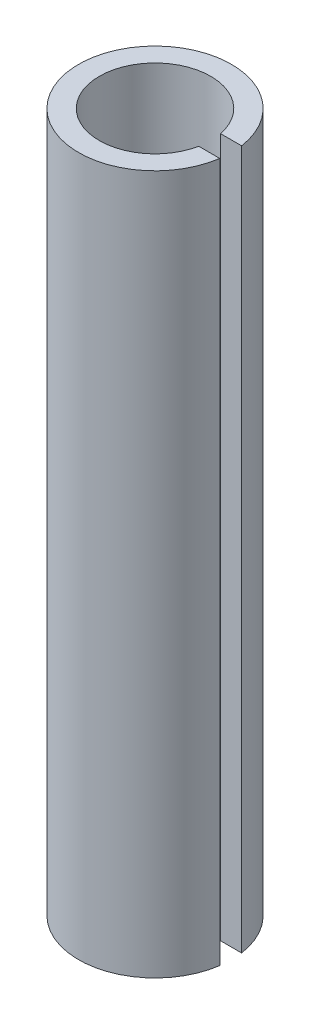
SolidWorks part; units mm, degrees
ref_plane "Front Plane" through (0, 0, 0) normal (0, 0, 1) x (1, 0, 0)
ref_plane "Top Plane" through (0, 0, 0) normal (0, 1, 0) x (1, 0, 0)
ref_plane "Right Plane" through (0, 0, 0) normal (1, 0, 0) x (0, 0, -1)
sketch "Sketch1" plane through (0, 0, 0) normal (0, 1, 0) x (1, 0, 0)
  line L0 (2.5005, 0.5) -> (3.4641, 0.5)
  line L1 (2.5005, -0.5) -> (3.4641, -0.5)
  line L2 (0, 0) -> (3.5, 0) construction
  circle A0 centre (0, 0) radius 3.5
  circle A1 centre (0, 0) radius 2.55
  dimension "D1" = 5.1
  dimension "D2" = 7
  dimension "D3" = 1
  dimension "D4" = 0.5
extrude "Boss-Extrude1" add sketch "Sketch1" along normal blind 32 contours A1 L0 A0 L1 region at (-2.6487, 0, 0)
